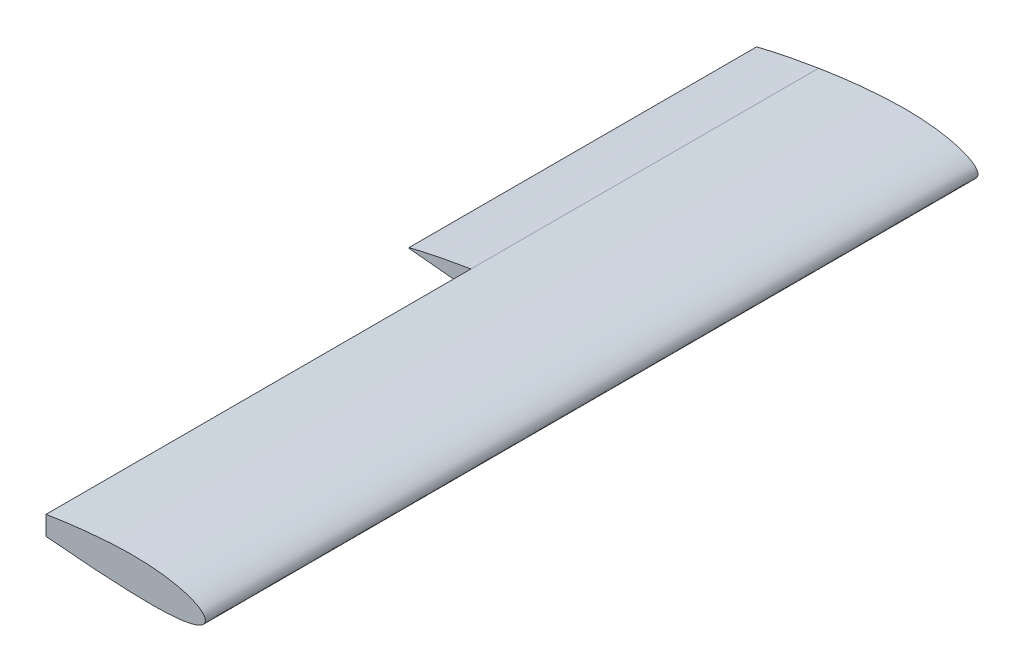
SolidWorks part; units mm, degrees
ref_plane "Front Plane" through (0, 0, 0) normal (0, 0, 1) x (1, 0, 0)
ref_plane "Top Plane" through (0, 0, 0) normal (0, 1, 0) x (1, 0, 0)
ref_plane "Right Plane" through (0, 0, 0) normal (1, 0, 0) x (0, 0, -1)
sketch "Sketch1" plane through (0, 0, 0) normal (0, 0, 1) x (1, 0, 0)
  line L0 (-230.9508, 18.5497) -> (-230.9508, -9.2543)
  spline S0 degree 3 poles (-230.9508, 18.5497) (-228.0495, 19.0122) (-221.2098, 20.1026) (-210.3095, 21.6942) (-198.1779, 23.3448) (-185.8013, 24.8762) (-173.2571, 26.268) (-160.6234, 27.4938) (-147.9795, 28.5305) (-135.3868, 29.3552) (-122.9015, 29.954) (-110.6006, 30.2332) (-98.5845, 30.1902) (-86.9568, 29.8182) (-75.7955, 29.1202) (-65.1756, 28.1047) (-55.1679, 26.7866) (-45.8384, 25.1864) (-37.2478, 23.33) (-29.4501, 21.2475) (-22.4931, 18.9719) (-16.4165, 16.538) (-11.2521, 13.9799) (-7.0224, 11.3279) (-3.7404, 8.6033) (-1.4142, 5.8093) (-0.0761, 2.9197) (0.1745, -0.0175) (-0.652, -2.8446) (-2.5184, -5.4132) (-5.3109, -7.7062) (-8.996, -9.7668) (-13.5586, -11.608) (-18.9775, -13.2303) (-25.2232, -14.6295) (-32.2591, -15.8018) (-40.0436, -16.7457) (-48.5308, -17.4629) (-57.6714, -17.959) (-67.413, -18.2439) (-77.7005, -18.3313) (-88.4762, -18.239) (-99.68, -17.9876) (-111.2496, -17.6014) (-123.1434, -17.1021) (-135.3121, -16.5233) (-147.6809, -15.8131) (-160.1528, -15.0012) (-172.6345, -14.109) (-185.0506, -13.1575) (-197.3255, -12.1663) (-209.3839, -11.1517) (-220.5687, -10.1827) (-227.7247, -9.5428) (-230.9508, -9.2543) knots 0 0 0 0 0.018424 0.043434 0.06908 0.095203 0.12164 0.148227 0.1748 0.201195 0.227364 0.253182 0.278347 0.30271 0.326128 0.348467 0.3696 0.389416 0.407811 0.424699 0.440008 0.453688 0.465715 0.476104 0.484928 0.49236 0.49873 0.504587 0.510443 0.516804 0.524199 0.532941 0.543186 0.554996 0.568376 0.583299 0.599709 0.617539 0.636704 0.657109 0.678651 0.701217 0.724685 0.748928 0.773811 0.799338 0.825326 0.851504 0.877716 0.9038 0.929596 0.954944 0.979688 1 1 1 1
extrude "Boss-Extrude1" add sketch "Sketch1" along normal blind 1120
sketch "Sketch2" plane through (0, 0, 0) normal (0, 0, 1) x (1, 0, 0)
  line L0 (-230.9508, 18.5497) -> (-230.9508, -9.2543)
  line L1 (-320.765, 0.5123) -> (-320.765, -0.5041)
  spline S0 degree 3 poles (-230.9508, 18.5497) (-231.8637, 18.4067) (-236.4436, 17.6893) (-244.5027, 16.319) (-254.9355, 14.4789) (-264.7762, 12.6466) (-273.9673, 10.8588) (-282.4535, 9.1392) (-290.1848, 7.5144) (-297.1155, 6.0094) (-303.2051, 4.6483) (-308.4182, 3.4537) (-312.7248, 2.4459) (-316.1, 1.6425) (-318.5247, 1.0579) (-319.9739, 0.7056) (-320.6133, 0.5494) (-320.765, 0.5123) knots 0 0 0 0 0.030252 0.151774 0.267626 0.37709 0.479485 0.574175 0.66057 0.73813 0.806369 0.864859 0.913229 0.951173 0.978451 0.994887 1 1 1 1
  spline S1 degree 3 poles (-230.9508, -9.2543) (-231.5339, -9.2025) (-235.782, -8.8249) (-243.5255, -8.1161) (-253.992, -7.1477) (-263.889, -6.2144) (-273.1542, -5.3269) (-281.7285, -4.4926) (-289.557, -3.719) (-296.5894, -3.0139) (-302.7801, -2.3837) (-308.0889, -1.8378) (-312.4807, -1.376) (-315.9277, -1.0227) (-318.4047, -0.7374) (-319.9003, -0.617) (-320.5749, -0.5034) (-320.7538, -0.504) (-320.765, -0.5041) knots 0 0 0 0 0.019463 0.141781 0.258505 0.3689 0.472262 0.567931 0.655294 0.733785 0.802892 0.862162 0.911205 0.949694 0.977373 0.994054 0.999628 1 1 1 1
extrude "Boss-Extrude2" add sketch "Sketch2" along normal blind 504
sketch "Sketch3" plane through (0, 0, 0) normal (0, 0, 1) x (1, 0, 0)
  circle A0 centre (-96.23, 6.014) radius 12.7
extrude "Cut-Extrude1" cut sketch "Sketch3" along normal blind 801
ref_plane "Plane1" through (0, 0, 330.7) normal (0, 0, 1) x (1, 0, 0)
sketch "Sketch4" plane through (0, 0, 330.7) normal (0, 0, 1) x (1, 0, 0)
  line L0 (-112.23, -19.05) -> (-80.23, -19.05)
  line L1 (-80.23, -19.05) -> (-80.23, 21.714)
  line L2 (-80.23, 21.714) -> (-112.23, 21.714)
  line L3 (-112.23, 21.714) -> (-112.23, -19.05)
extrude "Cut-Extrude2" cut sketch "Sketch4" along normal blind 46
ref_plane "Plane2" through (0, 0, 330.7) normal (0, 0, 1) x (1, 0, 0)
sketch "Sketch5" plane through (0, 0, 330.7) normal (0, 0, 1) x (1, 0, 0)
  line L0 (-286.612, -8.954) -> (-226.612, -8.954)
  line L1 (-226.612, -8.954) -> (-226.612, 3.046)
  line L2 (-226.612, 3.046) -> (-286.612, 3.046)
  line L3 (-286.612, 3.046) -> (-286.612, -8.954)
extrude "Cut-Extrude3" cut sketch "Sketch5" along normal blind 46
ref_plane "Plane3" through (0, 0, 534.5) normal (0, 0, 1) x (1, 0, 0)
sketch "Sketch6" plane through (0, 0, 534.5) normal (0, 0, 1) x (1, 0, 0)
  line L0 (-203.421, -16.843) -> (-149.421, -16.843)
  line L1 (-149.421, -16.843) -> (-149.421, 12.257)
  line L2 (-149.421, 12.257) -> (-203.421, 12.257)
  line L3 (-203.421, 12.257) -> (-203.421, -16.843)
extrude "Cut-Extrude4" cut sketch "Sketch6" along normal blind 64
ref_plane "Plane4" through (0, 0, -0.5) normal (0, 0, 1) x (1, 0, 0)
sketch "Sketch7" plane through (0, 0, -0.5) normal (0, 0, 1) x (1, 0, 0)
  line L0 (-234.736, 1.411) -> (-214.336, 1.411)
  line L1 (-214.336, 1.411) -> (-214.336, 8.211)
  line L2 (-214.336, 8.211) -> (-234.736, 8.211)
  line L3 (-234.736, 8.211) -> (-234.736, 1.411)
extrude "Cut-Extrude5" cut sketch "Sketch7" along normal blind 26
